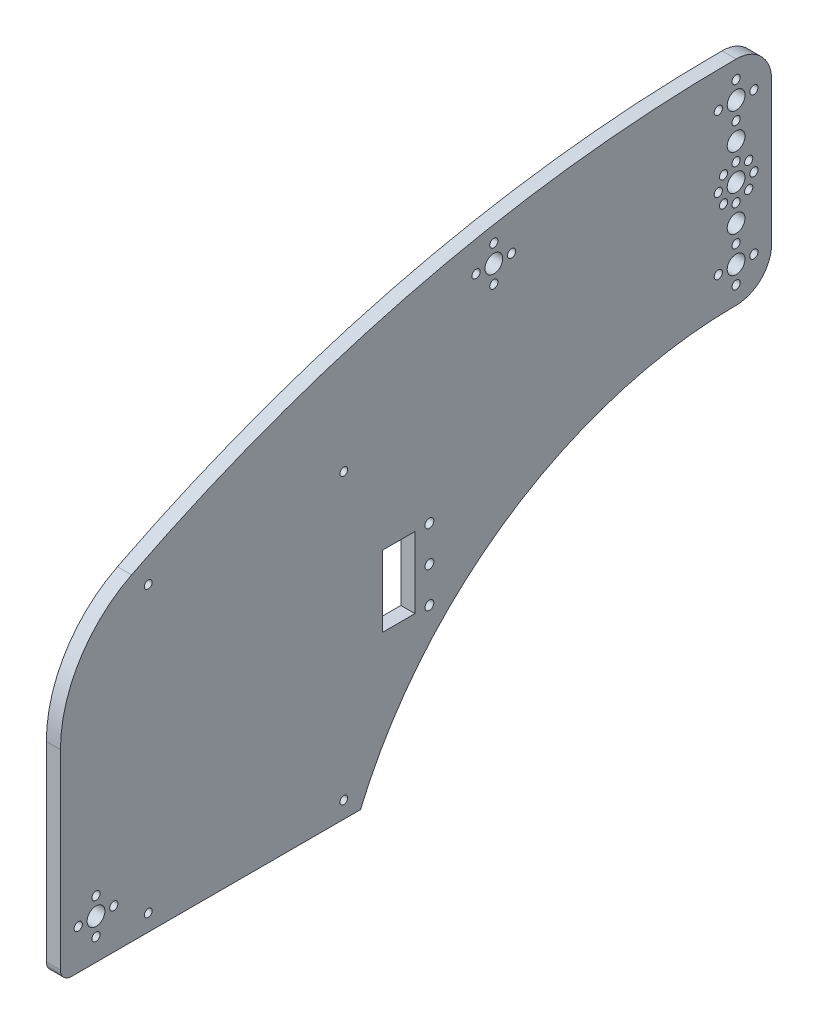
SolidWorks part; units mm, degrees
ref_plane "Front Plane" through (0, 0, 0) normal (0, 0, 1) x (1, 0, 0)
ref_plane "Top Plane" through (0, 0, 0) normal (0, 1, 0) x (1, 0, 0)
ref_plane "Right Plane" through (0, 0, 0) normal (1, 0, 0) x (0, 0, -1)
sketch "Sketch1" plane through (0, 0, 0) normal (1, 0, 0) x (0, 0, -1)
  line L0 (288, 110) -> (288, 126) construction
  line L1 (288, 110) -> (288, 118) construction
  line L2 (271.394, 142) -> (319.5261, 142) construction
  line L3 (288, 174) -> (288, 166) construction
  line L4 (288, 174) -> (288, 158) construction
  line L5 (-16, -18) -> (16, -18) construction
  line L6 (16, -18) -> (16, -50) construction
  line L7 (16, -50) -> (-16, -50) construction
  line L8 (-16, 72.9034) -> (-16, -13)
  line L9 (-11, -18) -> (119, -18)
  line L10 (304, 174) -> (304, 110)
  line L11 (23.5, 117.5) -> (23.5, -10.5) construction
  line L12 (16, 125) -> (119, 125) construction
  line L13 (16, 125) -> (16, -18) construction
  line L14 (16, -18) -> (119, -18) construction
  line L15 (119, 125) -> (119, -18) construction
  line L16 (23.5, -10.5) -> (111.5, -10.5) construction
  line L17 (111.5, 117.5) -> (111.5, -10.5) construction
  line L18 (23.5, 117.5) -> (111.5, 117.5) construction
  line L19 (129, 46.1421) -> (143.5, 46.1421)
  line L20 (129, 46.1421) -> (129, 78.1421)
  line L21 (143.5, 46.1421) -> (143.5, 78.1421)
  line L22 (129, 78.1421) -> (143.5, 78.1421)
  line L23 (150, 46.1421) -> (150, 78.1421) construction
  circle A0 centre (288, 110) radius 4
  circle A1 centre (288, 118) radius 1.85
  circle A2 centre (288, 126) radius 4
  circle A3 centre (288, 134) radius 1.85
  circle A4 centre (288, 142) radius 4
  circle A6 centre (288, 150) radius 1.85 [skipped]
  circle A7 centre (296, 110) radius 1.85
  circle A8 centre (288, 102) radius 1.85
  circle A9 centre (280, 110) radius 1.85
  circle A10 centre (282.3431, 136.3431) radius 1.85
  circle A11 centre (280, 142) radius 1.85
  circle A12 centre (282.3431, 147.6569) radius 1.85
  circle A13 centre (288, 150) radius 1.85
  circle A14 centre (293.6569, 147.6569) radius 1.85
  circle A15 centre (296, 142) radius 1.85
  circle A16 centre (293.6569, 136.3431) radius 1.85
  circle A17 centre (280, 174) radius 1.85
  circle A18 centre (288, 182) radius 1.85
  circle A19 centre (296, 174) radius 1.85
  circle A20 centre (288, 158) radius 4
  circle A21 centre (288, 166) radius 1.85
  circle A22 centre (288, 174) radius 4
  arc A23 (16, 125) -> (288, 190) centre (288, -411.6077) cw
  arc A24 (-16, -13) -> (-11, -18) centre (-11, -13) ccw
  arc A25 (288, 94) -> (119, -18) centre (288, -89.5045) ccw
  arc A26 (288, 190) -> (304, 174) centre (288, 174) cw
  arc A27 (304, 110) -> (288, 94) centre (288, 110) cw
  circle A28 centre (0, 0) radius 4
  circle A29 centre (8, 0) radius 1.85
  circle A30 centre (0, -8) radius 1.85
  circle A31 centre (-8, 0) radius 1.85
  circle A32 centre (0, 8) radius 1.85
  circle A33 centre (23.5, 117.5) radius 1.75
  circle A34 centre (111.5, 117.5) radius 1.75
  circle A35 centre (111.5, -10.5) radius 1.75
  circle A36 centre (23.5, -10.5) radius 1.75
  arc A37 (16, 125) -> (-16, 72.9034) centre (42.4072, 72.9034) ccw
  circle A38 centre (150, 46.1421) radius 2
  circle A39 centre (150, 62.1421) radius 2
  circle A40 centre (150, 78.1421) radius 2
  circle A41 centre (179, 164.7842) radius 4
  circle A42 centre (187, 164.7842) radius 1.85
  circle A43 centre (179, 156.7842) radius 1.85
  circle A44 centre (171, 164.7842) radius 1.85
  circle A45 centre (179, 172.7842) radius 1.85
  point P25 (288, 142)
  point P38 (288, 142)
  point P70 (0, -50)
  point P79 (0, 0)
  point P102 (202.3195, 162.9916)
  point P103 (217.0471, 167.6318)
  point P104 (241.2771, 173.1363)
  point P113 (179, 164.7842)
  dimension "D1" = 8
  dimension "D2" = 3.7
  dimension "D12" = 5
  dimension "D18" = 8
  dimension "D19" = 3.7
  dimension "D22" = 3.5
  dimension "D14" = 16
  dimension "D25" = 4
  dimension "D28" = 10
  dimension "D29" = 10
  dimension "D30" = 8
  dimension "D31" = 3.7
  dimension "D3" = 8
  dimension "D5" = 16
  dimension "D7" = 8
  dimension "D8" = 32
  dimension "D9" = 272
  dimension "D10" = 160
  dimension "D11" = 16
  dimension "D13" = 16
  dimension "D15" = 16
  dimension "D16" = 18
  dimension "D17" = 8
  dimension "D23" = 143
  dimension "D24" = 103
  dimension "D26" = 6.5
  dimension "D27" = 14.5
  dimension "D32" = 8
  dimension "D34" = 15
  dimension "D35" = 125
  dimension "D21" = 7.5
  dimension "D4" = 3
  dimension "D6" = 4
  dimension "D20" = 4
  dimension "D33" = 4
extrude "Boss-Extrude2" add sketch "Sketch1" along normal blind 6.35
